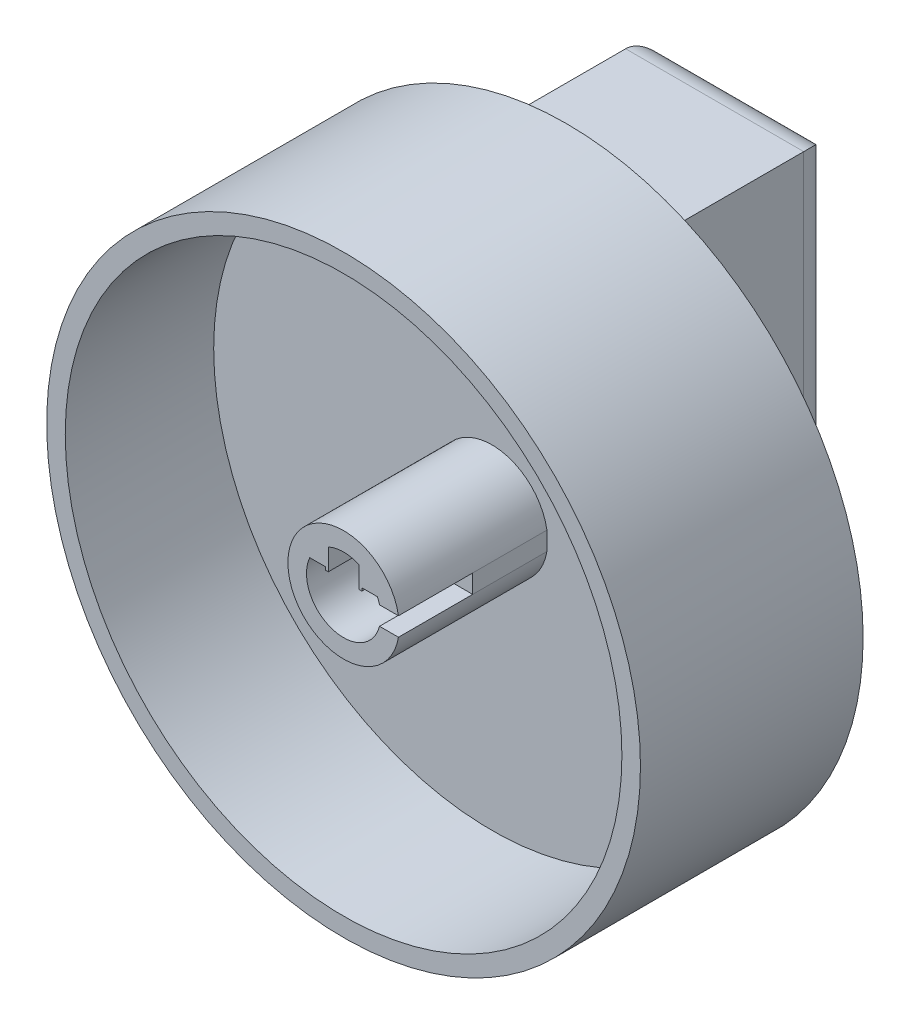
SolidWorks part; units mm, degrees
ref_plane "Front Plane" through (0, 0, 0) normal (0, 0, 1) x (1, 0, 0)
ref_plane "Top Plane" through (0, 0, 0) normal (0, 1, 0) x (1, 0, 0)
ref_plane "Right Plane" through (0, 0, 0) normal (1, 0, 0) x (0, 0, -1)
sketch "Sketch2" plane through (0, 0, 0) normal (0, 0, 1) x (1, 0, 0)
  line L0 (3.0742, 0.7938) -> (4.6959, 0.7937)
  line L1 (3.0742, -0.7937) -> (4.6959, -0.7937)
  circle A0 centre (0, 0) radius 25.4
  arc A1 (4.6959, 0.7937) -> (4.6959, -0.7937) centre (0, 0) ccw
  circle A2 centre (0, 0) radius 23.8125
  arc A3 (3.0742, 0.7938) -> (3.0742, -0.7937) centre (0, 0) ccw
  dimension "D1" = 50.8
  dimension "D2" = 9.525
  dimension "D3" = 47.625
  dimension "D4" = 6.35
  dimension "D5" = 1.5875
  dimension "D6" = 0.7937
extrude "Boss-Extrude1" add sketch "Sketch2" along normal blind 31.75 contours A3 L0 A1 L1 region at (-3.3092, 0, 0)
sketch "Sketch4" plane through (0, 0, 31.75) normal (0, 0, 1) x (1, 0, 0)
  circle A0 centre (0, 0) radius 25.4
  circle A1 centre (0, 0) radius 23.8125
  dimension "D1" = 50.8
  dimension "D2" = 47.625
extrude "Boss-Extrude3" add sketch "Sketch4" against normal blind 12.7 separate body
sketch "Sketch5" plane through (0, 0, 0) normal (0, 0, 1) x (1, 0, 0)
  line L0 (3.0742, 0.7938) -> (4.6959, 0.7937) construction
  line L1 (3.0742, 0.7938) -> (4.6959, 0.7937)
  line L2 (3.0742, 0.7938) -> (3.0742, -0.7937)
  line L3 (3.0742, -0.7937) -> (4.6959, -0.7937)
  line L4 (4.6959, 0.7937) -> (4.6959, -0.7937)
  line L5 (3.0742, -0.7937) -> (4.6959, -0.7937) construction
  point P8 (0, 0)
  point P10 (4.5794, 0.7938)
  point P11 (0, 0)
extrude "Boss-Extrude4" add sketch "Sketch5" along normal blind 25.4
sketch "Sketch6" plane through (0, 0, 0) normal (0, 0, 1) x (1, 0, 0)
  line L0 (-1.3063, 2.8938) -> (-1.3063, 1.3063)
  line L1 (-1.5603, 1.3063) -> (-2.8938, 1.3063)
  line L2 (1.3063, 2.8938) -> (1.3063, 1.3063)
  line L3 (1.3063, 1.3063) -> (2.8938, 1.3063)
  line L4 (-1.3063, 1.3063) -> (-1.3063, 1.0523)
  line L5 (-1.3063, 1.0523) -> (-1.5603, 1.0523)
  line L6 (-1.5603, 1.0523) -> (-1.5603, 1.3063)
  line L7 (1.3063, 1.3063) -> (1.3063, 1.0523)
  line L8 (1.3063, 1.0523) -> (1.5603, 1.0523)
  line L9 (1.5603, 1.0523) -> (1.5603, 1.3063)
  arc A0 (-1.3063, 2.8938) -> (-2.8938, 1.3063) centre (-1.3063, 1.3063) ccw
  arc A1 (2.8938, 1.3063) -> (1.3063, 2.8938) centre (1.3063, 1.3063) ccw
  arc A2 (3.0742, 0.7938) -> (3.0742, -0.7937) centre (0, 0) ccw construction
  dimension "D1" = 1.5875
  dimension "D2" = 0.254
  dimension "D3" = 1.5875
  dimension "D4" = 0.254
  dimension "D5" = 0.254
  dimension "D6" = 0.254
extrude "Boss-Extrude5" add sketch "Sketch6" along normal up to surface (31.75 mm away) contours L0 A0 L1 L6 L5 L4 | L3 A1 L2 | L8 L9 L3 L7 region at (-1.9628, 1.9548, 0) region at (1.9801, 1.9801, 0) region at (1.4333, 1.1793, 0) up to face at (-0.0419, 0, 31.75)
sketch "Sketch9" plane through (0, 0, 19.05) normal (0, 0, -1) x (-1, 0, 0)
  circle A0 centre (0, 0) radius 25.4
  circle A1 centre (0, 0) radius 4.5938
  arc A2 (-4.6959, -0.7937) -> (-4.6959, 0.7937) centre (0, 0) ccw construction
  dimension "D1" = 50.8
extrude "Boss-Extrude6" add sketch "Sketch9" along normal blind 6.35
sketch "Sketch10" plane through (0, 0, 12.7) normal (0, 0, -1) x (-1, 0, 0)
  line L1 (-5.08, -18.4752) -> (5.08, -18.4752)
  line L2 (-5.08, -18.4752) -> (-5.08, 18.4752)
  line L3 (-5.08, 18.4752) -> (5.08, 18.4752)
  line L4 (5.08, -18.4752) -> (5.08, 18.4752)
  line L5 (-5.08, -18.4752) -> (5.08, 18.4752) construction
  line L6 (-5.08, 18.4752) -> (5.08, -18.4752) construction
  line L7 (-7.62, -20.772) -> (7.62, -20.772)
  line L8 (-7.62, -20.772) -> (-7.62, 20.772)
  line L9 (-7.62, 20.772) -> (7.62, 20.772)
  line L10 (7.62, -20.772) -> (7.62, 20.772)
  line L11 (-7.62, -20.772) -> (7.62, 20.772) construction
  line L12 (-7.62, 20.772) -> (7.62, -20.772) construction
  point P0 (0, 0)
  point P6 (0, 0)
  dimension "D1" = 5.08
  dimension "D2" = 7.62
extrude "Boss-Extrude7" add sketch "Sketch10" along normal up to surface (12.7 mm away) up to face at (0.4179, 1.0213, 0)
sketch "Sketch11" plane through (0, 0, 0) normal (0, 0, -1) x (-1, 0, 0)
  line L0 (7.62, 20.772) -> (-7.62, 20.772) construction
  line L1 (-7.62, -20.772) -> (7.62, -20.772)
  line L2 (-7.62, -20.772) -> (-7.62, 20.772)
  line L3 (-7.62, 20.772) -> (7.62, 20.772)
  line L4 (7.62, -20.772) -> (7.62, 20.772)
  line L5 (-7.62, -20.772) -> (7.62, 20.772) construction
  line L6 (-7.62, 20.772) -> (7.62, -20.772) construction
  line L7 (-7.62, 20.772) -> (-7.62, -20.772) construction
  point P0 (0, 0)
extrude "Boss-Extrude8" add sketch "Sketch11" along normal blind 2.54
fillet "Fillet1" radius 2.54 4 edges at (0, 20.772, 12.7) (-7.62, 0, 12.7) (0, -20.772, 12.7) (7.62, 0, 12.7)
fillet "Fillet2" radius 2.54 4 edges at (0, -20.772, -2.54) (-7.62, 0, -2.54) (0, 20.772, -2.54) (7.62, 0, -2.54)
sketch "Sketch12" plane through (0, 0, 12.7) normal (0, 0, -1) x (-1, 0, 0)
  line L0 (16.8139, 14.7045) -> (17.5476, 16.7222)
  line L1 (17.5476, 16.7222) -> (18.4891, 14.7045)
  line L2 (16.8139, 14.7045) -> (15.591, 18.6787)
  line L3 (15.591, 18.6787) -> (14.6128, 14.7045)
  line L4 (14.6128, 14.7045) -> (14.0014, 16.6916)
  line L5 (14.0014, 16.6916) -> (13.5122, 14.7045)
  line L6 (22.6527, 5.3719) -> (23.453, 5.3719)
  line L7 (23.453, 5.3719) -> (23.453, -1.9992)
  line L8 (23.453, -1.9992) -> (22.6527, -1.9992)
  line L9 (22.6527, -1.9992) -> (22.6527, 1.0335)
  line L10 (22.6527, 1.0335) -> (20.7573, 1.0335)
  line L11 (20.7573, 1.0335) -> (20.7573, -1.9992)
  line L12 (20.7573, -1.9992) -> (19.6622, -1.9992)
  line L13 (19.6622, -1.9992) -> (19.6622, 5.3719)
  line L14 (19.6622, 5.3719) -> (20.7573, 5.3719)
  line L15 (20.7573, 5.3719) -> (20.7573, 2.5498)
  line L16 (20.7573, 2.5498) -> (22.6527, 2.5498)
  line L17 (22.6527, 2.5498) -> (22.6527, 5.3719)
  line L18 (-23.6362, 5.3719) -> (-23.6362, -1.9992)
  line L19 (-23.6362, -1.9992) -> (-19.5282, -1.9992)
  line L20 (-19.5282, -1.9992) -> (-19.5282, -0.9456)
  line L21 (-19.5282, -0.9456) -> (-22.1259, -0.9456)
  line L22 (-22.1259, -0.9456) -> (-22.1259, 5.3719)
  line L23 (-22.1259, 5.3719) -> (-23.6362, 5.3719)
  spline S0 degree 3 poles (18.4891, 14.7045) (19.7988, 12.7861) (18.3108, 9.6473) (13.1858, 9.2264) (12.6936, 13.3378) (13.5122, 14.7045) knots 0 0 0 0 0.43295 0.596957 1 1 1 1
extrude "Cut-Extrude1" cut sketch "Sketch12" against normal blind 2.54
